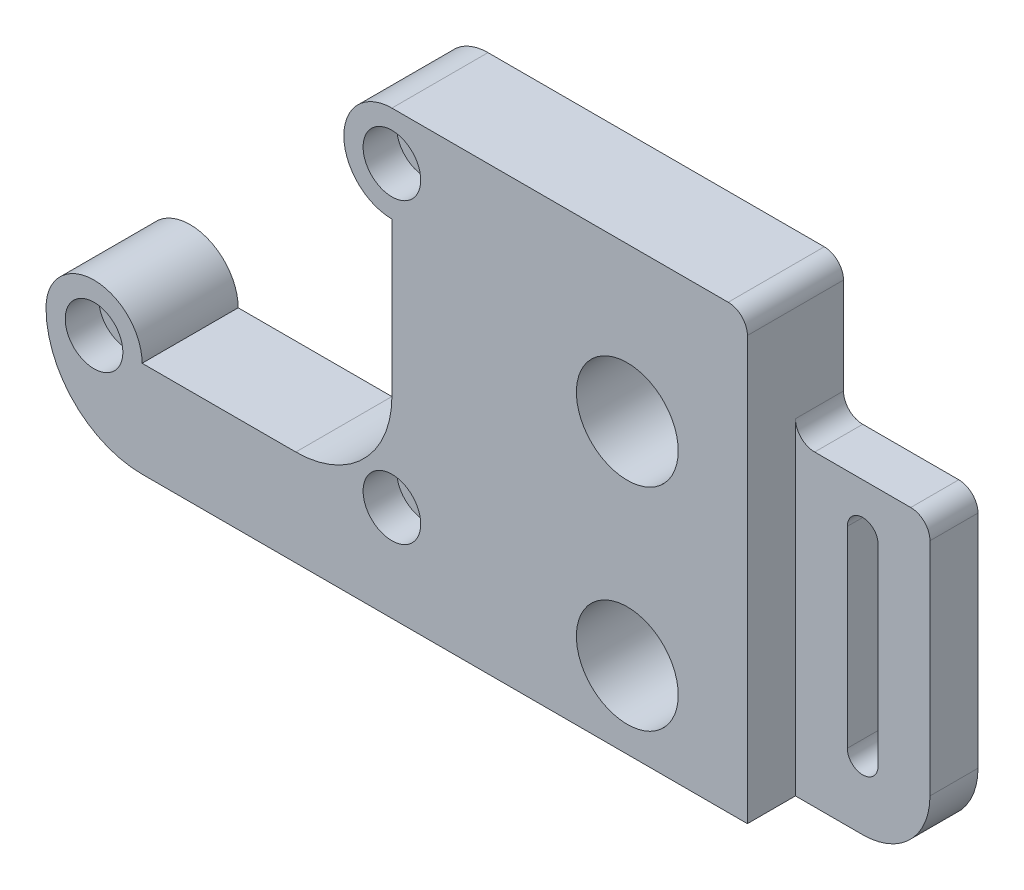
SolidWorks part; units mm, degrees
ref_plane "Front Plane" through (0, 0, 0) normal (0, 0, 1) x (1, 0, 0)
ref_plane "Top Plane" through (0, 0, 0) normal (0, 1, 0) x (1, 0, 0)
ref_plane "Right Plane" through (0, 0, 0) normal (1, 0, 0) x (0, 0, -1)
sketch "Sketch1" plane through (0, 0, 0) normal (0, 0, 1) x (1, 0, 0)
  line L0 (0, -5) -> (0, 5) construction
  line L1 (0, 5) -> (35, 5)
  line L2 (-26, -41) -> (44, -41)
  line L3 (51, -11) -> (51, -34)
  line L4 (44, -34) -> (44, -14) construction
  line L5 (42.4, -34) -> (42.4, -14)
  line L6 (45.6, -34) -> (45.6, -14)
  line L7 (49, -9) -> (39, -9)
  line L8 (19.2, -33) -> (29.8, -33) construction
  line L9 (24.5, -11) -> (24.5, -33) construction
  line L10 (0, -5) -> (0, -21)
  line L11 (-10, -31) -> (0, -31) construction
  line L12 (-31, -31) -> (-26, -31) construction
  line L13 (37, -7) -> (37, 3)
  line L14 (-10, -31) -> (-26, -31)
  line L15 (0, -31) -> (0, -21) construction
  line L16 (24.5, -33) -> (24.5, -41) construction
  line L17 (-31, -31) -> (-36, -31) construction
  arc A0 (0, 5) -> (0, -5) centre (0, 0) ccw
  circle A1 centre (0, 0) radius 1.8
  arc A2 (51, -11) -> (49, -9) centre (49, -11) ccw
  arc A3 (51, -34) -> (44, -41) centre (44, -34) cw
  arc A4 (42.4, -34) -> (45.6, -34) centre (44, -34) ccw
  circle A5 centre (24.5, -33) radius 5.3
  circle A6 centre (24.5, -11) radius 5.3
  circle A7 centre (0, -31) radius 1.8
  arc A8 (-26, -31) -> (-36, -31) centre (-31, -31) ccw
  circle A9 centre (-31, -31) radius 1.8
  arc A10 (45.6, -14) -> (42.4, -14) centre (44, -14) ccw
  arc A11 (-10, -31) -> (0, -21) centre (-10, -21) ccw
  arc A12 (-36, -31) -> (-26, -41) centre (-26, -31) ccw
  arc A13 (39, -9) -> (37, -7) centre (39, -7) cw
  arc A14 (35, 5) -> (37, 3) centre (35, 3) cw
  point P6 (44, -24)
  dimension "D1" = 10
  dimension "D2" = 3.6
  dimension "D4" = 14
  dimension "D8" = 10.6
  dimension "D9" = 22
  dimension "D10" = 31
  dimension "D12" = 20
  dimension "D13" = 2
  dimension "D7" = 2
  dimension "D11" = 7
  dimension "D5" = 10
  dimension "D14" = 70
  dimension "D6" = 3.2
  dimension "D3" = 24.5
  dimension "D15" = 14
extrude "Boss-Extrude1" add sketch "Sketch1" along normal blind 10
sketch "Sketch2" plane through (0, 0, 10) normal (0, 0, 1) x (1, 0, 0)
  circle A0 centre (-31, -31) radius 3
  circle A1 centre (0, -31) radius 3
  circle A2 centre (0, 0) radius 3
  dimension "D1" = 6
extrude "Cut-Extrude1" cut sketch "Sketch2" against normal blind 3.5
sketch "Sketch3" plane through (0, 0, 10) normal (0, 0, 1) x (1, 0, 0)
  line L0 (37, -41) -> (37, 5)
  line L1 (-26, -41) -> (44, -41) construction
  line L2 (0, 5) -> (35, 5) construction
  line L3 (37, -41) -> (44, -41)
  line L4 (37, 5) -> (51, 5)
  line L5 (51, 5) -> (51, -34)
  arc A0 (44, -41) -> (51, -34) centre (44, -34) ccw
  arc M6 (45.6, -34) -> (42.4, -34) centre (44, -34) cw
  line M12 (-26, -41) -> (44, -41)
  arc M13 (44, -41) -> (51, -34) centre (44, -34) ccw
  line M14 (51, -34) -> (51, -11)
  line M16 (35, 5) -> (0, 5)
  arc M35 (37, 3) -> (35, 5) centre (35, 3) ccw
  arc M36 (51, -11) -> (49, -9) centre (49, -11) ccw
  line M37 (49, -9) -> (39, -9)
  arc M38 (39, -9) -> (37, -7) centre (39, -7) cw
  line M39 (37, -7) -> (37, 3)
  arc M40 (42.4, -14) -> (45.6, -14) centre (44, -14) cw
  line M41 (45.6, -14) -> (45.6, -34)
  line M42 (42.4, -34) -> (42.4, -14)
extrude "Cut-Extrude2" cut sketch "Sketch3" against normal blind 5 contours L0 M12 M13 M14 M36 M37 M38 M39 M35 M16 M42 M40 M41 M6 | L5 L4 M35 M39 M38 M37 M36
